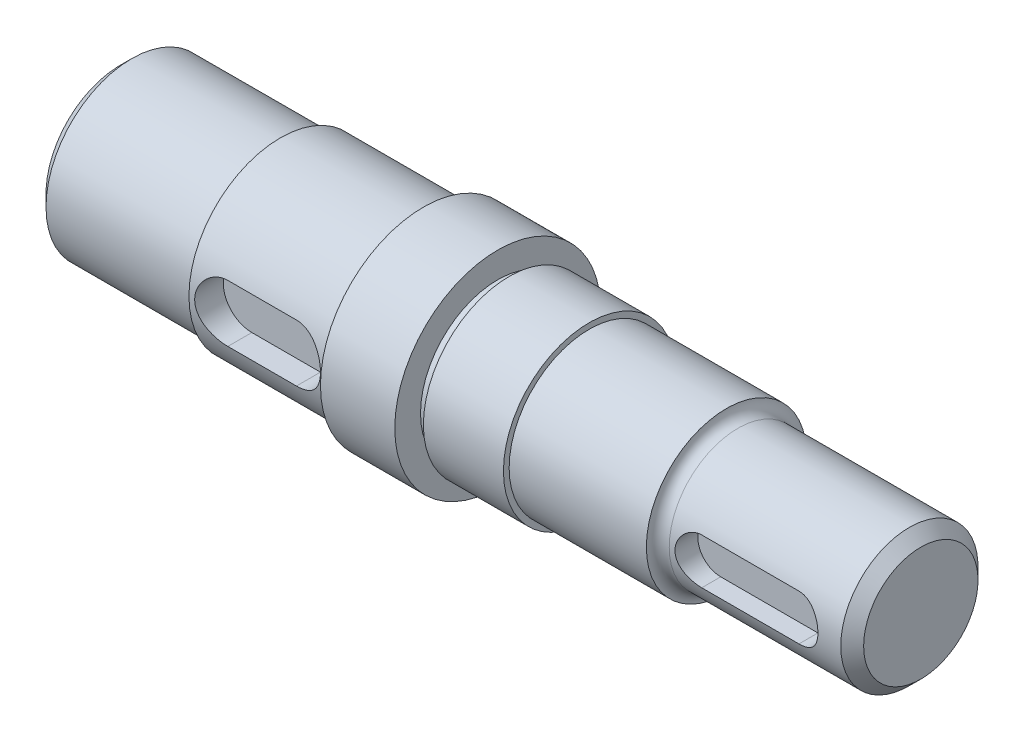
SolidWorks part; units mm, degrees
material "AISI 1045 钢，冷拔"
ref_plane "前视基准面" through (0, 0, 0) normal (0, 0, 1) x (1, 0, 0)
ref_plane "上视基准面" through (0, 0, 0) normal (0, 1, 0) x (1, 0, 0)
ref_plane "右视基准面" through (0, 0, 0) normal (1, 0, 0) x (0, 0, -1)
sketch "草图1" plane through (0, 0, 0) normal (0, 0, 1) x (1, 0, 0)
  line L0 (0, 61.488) -> (0, 0) construction
  line L1 (0, 0) -> (158.144, 0) construction
  line L2 (0, 0) -> (0, 15)
  line L3 (0, 15) -> (28, 15)
  line L4 (28, 15) -> (28, 16)
  line L5 (28, 16) -> (53, 16)
  line L6 (53, 16) -> (53, 18)
  line L7 (53, 18) -> (66, 18)
  line L8 (66, 18) -> (66, 13.5)
  line L9 (66, 13.5) -> (68, 13.5)
  line L10 (68, 13.5) -> (68, 15)
  line L11 (68, 15) -> (82, 15)
  line L12 (82, 15) -> (82, 14)
  line L13 (82, 14) -> (106, 14)
  line L14 (106, 14) -> (106, 12)
  line L15 (106, 12) -> (140, 12)
  line L16 (140, 12) -> (140, 0)
  line L17 (140, 0) -> (0, 0)
  dimension "D1" = 140
  dimension "D2" = 74
  dimension "D3" = 16
  dimension "D4" = 34
  dimension "D5" = 13
  dimension "D6" = 25
  dimension "D7" = 30
  dimension "D8" = 32
  dimension "D9" = 36
  dimension "D10" = 30
  dimension "D11" = 28
  dimension "D12" = 24
  dimension "D13" = 2
  dimension "D14" = 1.5
revolve "旋转1" add sketch "草图1" angle 360 about L1
ref_plane "基准面1" through (0, 0, 20) normal (0, 0, 1) x (1, 0, 0)
sketch "草图2" plane through (0, 0, 20) normal (0, 0, 1) x (1, 0, 0)
  line L0 (140, 0) -> (98.5782, 0) construction
  line L1 (140, -12) -> (140, 12) construction
  line L2 (113, 4) -> (130, 4)
  line L3 (106, -14) -> (106, 14) construction
  line L4 (113, -4) -> (130, -4)
  arc A0 (113, 4) -> (113, -4) centre (113, 0) ccw
  arc A1 (130, -4) -> (130, 4) centre (130, 0) ccw
  dimension "D1" = 8
  dimension "D2" = 17
  dimension "D3" = 7
extrude "切除-拉伸1" cut sketch "草图2" against normal offset from surface (12 mm away) 8 up to plane "前视基准面"
sketch "草图3" plane through (0, 0, 20) normal (0, 0, 1) x (1, 0, 0)
  line L0 (0, 0) -> (72.2022, 0) construction
  line L1 (53, 16) -> (53, -16) construction
  line L2 (34, 5) -> (46, 5)
  line L3 (34, -5) -> (46, -5)
  arc A0 (34, 5) -> (34, -5) centre (34, 0) ccw
  arc A1 (46, -5) -> (46, 5) centre (46, 0) ccw
  dimension "D1" = 10
  dimension "D2" = 12
  dimension "D3" = 7
extrude "切除-拉伸2" cut sketch "草图3" against normal offset from surface (9 mm away) 11 up to plane "前视基准面"
chamfer "倒角1" distance 2 angle 45 2 edges at (0, 0, 15) (140, 0, 12)
fillet "圆角1" radius 2 1 edges at (106, 0, 12)
